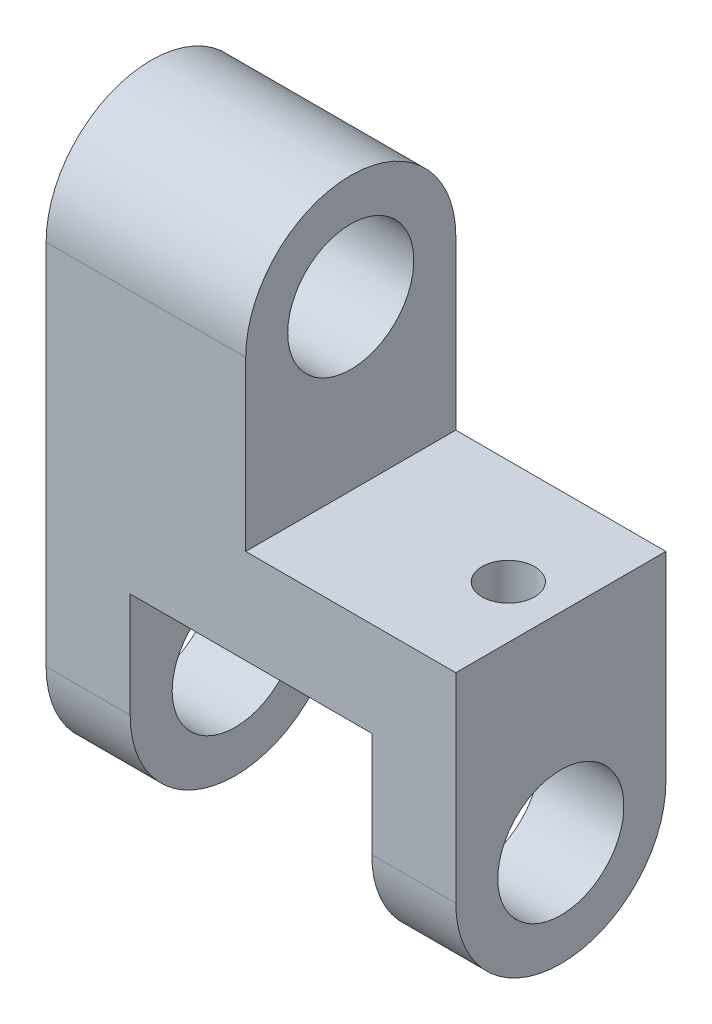
SolidWorks part; units mm, degrees
ref_plane "Спереди" through (0, 0, 0) normal (0, 0, 1) x (1, 0, 0)
ref_plane "Сверху" through (0, 0, 0) normal (0, 1, 0) x (1, 0, 0)
ref_plane "Справа" through (0, 0, 0) normal (1, 0, 0) x (0, 0, -1)
sketch "Эскиз1" plane through (0, 0, 0) normal (1, 0, 0) x (0, 0, -1)
  line L0 (0, 17.5) -> (0, -17.5) construction
  line L1 (10, 17.5) -> (10, -17.5)
  line L2 (-10, 17.5) -> (-10, -17.5)
  line L3 (-17.287, 0) -> (16.9614, 0) construction
  arc A0 (10, 17.5) -> (-10, 17.5) centre (0, 17.5) ccw
  arc A1 (-10, -17.5) -> (10, -17.5) centre (0, -17.5) ccw
  circle A2 centre (0, 17.5) radius 6
  circle A3 centre (0, -17.5) radius 6
  point P3 (0, 0)
  dimension "D1" = 55
  dimension "D3" = 12
  dimension "D2" = 20
extrude "Бобышка-Вытянуть1" add sketch "Эскиз1" along normal blind 39
sketch "Эскиз2" plane through (0, 0, 0) normal (0, 0, 1) x (1, 0, 0)
  line L0 (0, 17.5) -> (0, -17.5) construction
  line L1 (8, -7.5) -> (31, -7.5)
  line L2 (8, -7.5) -> (8, -40.5924)
  line L3 (8, -40.5924) -> (31, -40.5924)
  line L4 (31, -7.5) -> (31, -40.5924)
  line L5 (39, 17.5) -> (39, -17.5) construction
  line L6 (0, -27.5) -> (39, -27.5) construction
  dimension "D1" = 8
  dimension "D2" = 8
  dimension "D3" = 20
extrude "Вырез-Вытянуть1" cut sketch "Эскиз2" against normal through all and the other way through all
sketch "Эскиз3" plane through (0, 0, 0) normal (0, 0, 1) x (1, 0, 0)
  line L0 (0, 17.5) -> (0, -17.5) construction
  line L1 (19, 35.0973) -> (62.7132, 35.0973)
  line L2 (19, 35.0973) -> (19, 1.5)
  line L3 (19, 1.5) -> (62.7132, 1.5)
  line L4 (62.7132, 35.0973) -> (62.7132, 1.5)
  line L5 (31, -7.5) -> (8, -7.5) construction
  point P4 (53.7103, 6.2085)
  dimension "D1" = 19
  dimension "D2" = 9
extrude "Вырез-Вытянуть2" cut sketch "Эскиз3" against normal through all and the other way through all
sketch "Эскиз4" plane through (0, 1.5, 0) normal (0, 1, 0) x (1, 0, 0)
  line L0 (23.1159, 0) -> (39, 0) construction
  line L1 (39, -10) -> (39, 10) construction
  circle A0 centre (34, 0) radius 2.5
  point P6 (0, 0)
  dimension "D1" = 5
  dimension "D2" = 5
extrude "Вырез-Вытянуть3" cut sketch "Эскиз4" against normal blind 10
